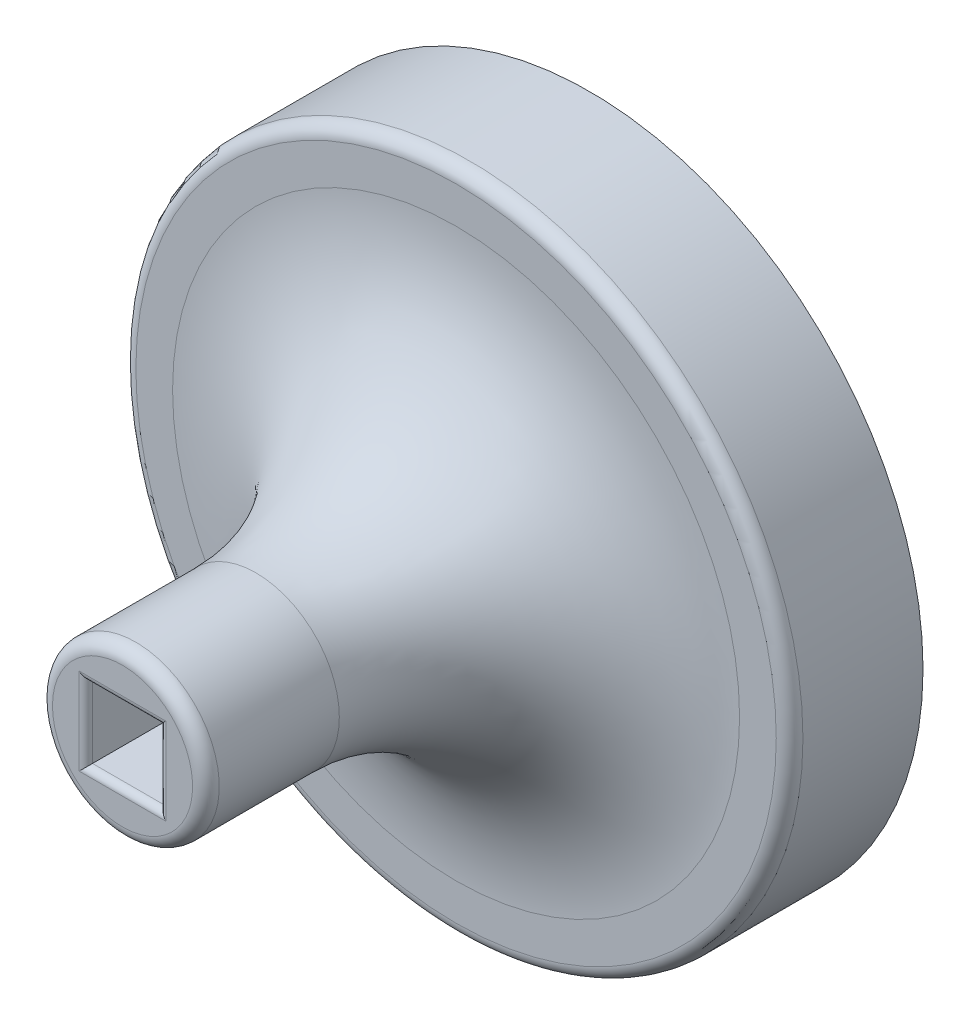
SolidWorks part; units mm, degrees
ref_plane "Plan de face" through (0, 0, 0) normal (0, 0, 1) x (1, 0, 0)
ref_plane "Plan de dessus" through (0, 0, 0) normal (0, 1, 0) x (1, 0, 0)
ref_plane "Plan de droite" through (0, 0, 0) normal (1, 0, 0) x (0, 0, -1)
sketch "Esquisse1" plane through (0, 0, 0) normal (0, 0, 1) x (1, 0, 0)
  circle A0 centre (0, 0) radius 25
  dimension "D1" = 50
extrude "Boss.-Extru.1" add sketch "Esquisse1" along normal blind 10
sketch "Esquisse2" plane through (0, 0, 0) normal (0, 0, -1) x (-1, 0, 0)
  circle A0 centre (0, 0) radius 6.25
  dimension "D1" = 12.5
extrude "Boss.-Extru.2" add sketch "Esquisse2" against normal blind 35
sketch "Esquisse3" plane through (0, 0, 0) normal (0, 0, -1) x (-1, 0, 0)
  line L1 (-2.75, 2.75) -> (2.75, 2.75)
  line L2 (-2.75, 2.75) -> (-2.75, -2.75)
  line L3 (-2.75, -2.75) -> (2.75, -2.75)
  line L4 (2.75, 2.75) -> (2.75, -2.75)
  line L5 (-2.75, 2.75) -> (2.75, -2.75) construction
  line L6 (-2.75, -2.75) -> (2.75, 2.75) construction
  point P0 (0, 0)
  dimension "D1" = 5.5
extrude "Enlèv. mat.-Extru.1" cut sketch "Esquisse3" against normal blind 40
fillet "Congé1" radius 15 1 edges at (6.25, 0, 10)
fillet "Congé2" radius 1 2 edges at (25, 0, 10) (-6.25, 0, 35)
fillet "Congé4" radius 0.5 4 edges at (-2.75, 0, 35) (0, 2.75, 35) (2.75, 0, 35) (0, -2.75, 35)
